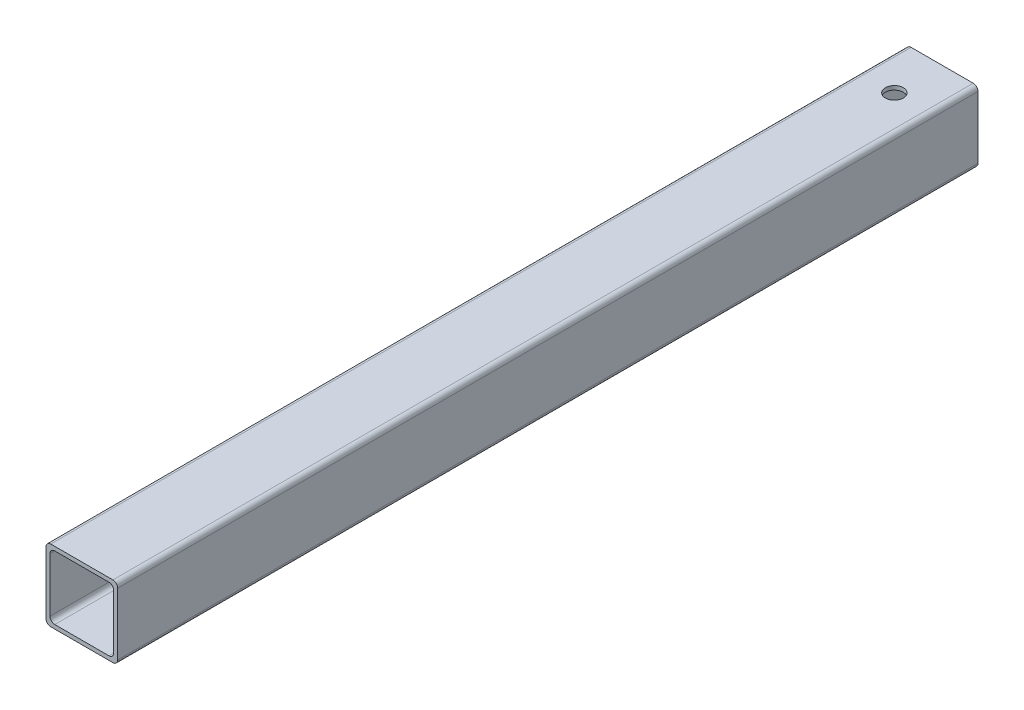
SolidWorks part; units mm, degrees
ref_plane "Front Plane" through (0, 0, 0) normal (0, 0, 1) x (1, 0, 0)
ref_plane "Top Plane" through (0, 0, 0) normal (0, 1, 0) x (1, 0, 0)
ref_plane "Right Plane" through (0, 0, 0) normal (1, 0, 0) x (0, 0, -1)
sketch "Sketch1" plane through (0, 0, 0) normal (0, 0, 1) x (1, 0, 0)
  line L0 (-16.9418, 16.9418) -> (16.9418, 16.9418)
  line L1 (-19.05, -19.05) -> (19.05, -19.05)
  line L2 (-19.05, -19.05) -> (-19.05, 19.05)
  line L3 (-19.05, 19.05) -> (19.05, 19.05)
  line L4 (19.05, -19.05) -> (19.05, 19.05)
  line L5 (-19.05, -19.05) -> (19.05, 19.05) construction
  line L6 (-19.05, 19.05) -> (19.05, -19.05) construction
  line L7 (16.9418, -16.9418) -> (16.9418, 16.9418)
  line L8 (-16.9418, -16.9418) -> (16.9418, -16.9418)
  line L9 (-16.9418, -16.9418) -> (-16.9418, 16.9418)
  point P0 (0, 0)
  dimension "D1" = 38.1
  dimension "D2" = 38.1
  dimension "D3" = 2.1082
extrude "Boss-Extrude1" add sketch "Sketch1" along normal blind 457.2
fillet "Fillet1" radius 2.54 8 edges at (19.05, -19.05, 228.6) (16.9418, -16.9418, 228.6) (16.9418, 16.9418, 228.6) (19.05, 19.05, 228.6) (-16.9418, 16.9418, 228.6) (-19.05, 19.05, 228.6) (-16.9418, -16.9418, 228.6) (-19.05, -19.05, 228.6)
ref_axis "Axis1" through (0, 0, -22.86) along (0, 0, 1)
sketch "Sketch2" plane through (0, 19.05, 0) normal (0, 1, 0) x (1, 0, 0)
  line L0 (0, 22.86) -> (0, -480.06) construction
  line L1 (16.51, 0) -> (-16.51, 0) construction
  circle A0 centre (0, -25.4) radius 4.7625
  dimension "D2" = 9.525
  dimension "D1" = 25.4
extrude "Cut-Extrude1" cut sketch "Sketch2" against normal through all
